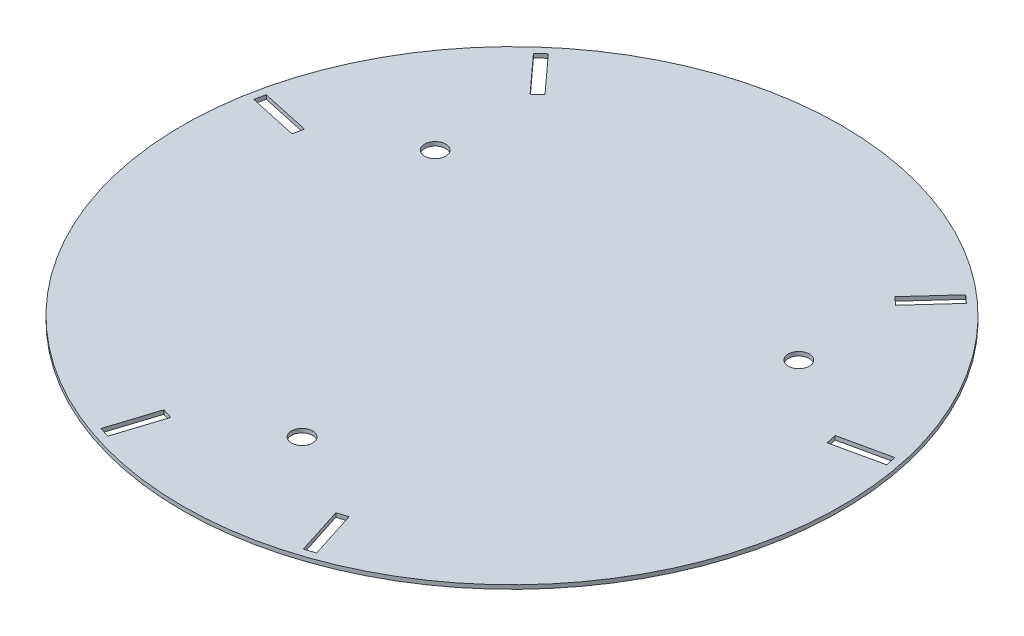
SolidWorks part; units mm, degrees
ref_plane "Front Plane" through (0, 0, 0) normal (0, 0, 1) x (1, 0, 0)
ref_plane "Top Plane" through (0, 0, 0) normal (0, 1, 0) x (1, 0, 0)
ref_plane "Right Plane" through (0, 0, 0) normal (1, 0, 0) x (0, 0, -1)
sketch "Sketch2" plane through (0, 0, 0) normal (0, 1, 0) x (1, 0, 0)
  circle A0 centre (0, 0) radius 125
  dimension "D1" = 250
extrude "Boss-Extrude1" add sketch "Sketch2" along normal blind 1.5 contours A0
sketch "Sketch3" plane through (0, 1.5, 0) normal (0, 1, 0) x (1, 0, 0)
  line L0 (0, 0) -> (-38, -119.084) construction
  line L1 (-270.1917, -358.6733) -> (-267.1917, -358.6733)
  line L2 (-270.1917, -358.6733) -> (-270.1917, -377.6733)
  line L3 (-270.1917, -377.6733) -> (-267.1917, -377.6733)
  line L4 (-267.1917, -358.6733) -> (-267.1917, -377.6733)
  line L9 (-38, -119.084) -> (38, -119.084) construction
  line L10 (0, 0) -> (0, -293.8403) construction
  line L11 (31.312, -98.1252) -> (35.1227, -96.9092)
  line L12 (37.088, -116.226) -> (40.8987, -115.01)
  line L14 (37.088, -116.226) -> (31.312, -98.1252)
  line L15 (40.8987, -115.01) -> (35.1227, -96.9092)
  line L17 (-38, -119.084) -> (-37.088, -116.226) construction
  line L19 (-37.088, -116.226) -> (-31.312, -98.1252)
  line L20 (-37.088, -116.226) -> (-40.8987, -115.01)
  line L21 (-31.312, -98.1252) -> (-35.1227, -96.9092)
  line L22 (-40.8987, -115.01) -> (-35.1227, -96.9092)
  line L52 (-82.1107, 90.2321) -> (-69.3229, 76.1796)
  line L53 (-82.1107, 90.2321) -> (-79.1522, 92.9243)
  line L54 (-79.1522, 92.9243) -> (-66.3645, 78.8717)
  line L55 (-69.3229, 76.1796) -> (-66.3645, 78.8717)
  line L56 (-100.6349, 21.9456) -> (-101.4872, 18.0375)
  line L57 (-120.0509, 22.0857) -> (-101.4872, 18.0375)
  line L58 (-119.1987, 25.9938) -> (-120.0509, 22.0857)
  line L59 (-119.1987, 25.9938) -> (-100.6349, 21.9456)
  line L60 (119.1987, 25.9938) -> (100.6349, 21.9456)
  line L61 (119.1987, 25.9938) -> (120.0509, 22.0857)
  line L62 (120.0509, 22.0857) -> (101.4872, 18.0375)
  line L63 (100.6349, 21.9456) -> (101.4872, 18.0375)
  line L64 (69.3229, 76.1796) -> (66.3645, 78.8717)
  line L65 (79.1522, 92.9243) -> (66.3645, 78.8717)
  line L66 (82.1107, 90.2321) -> (79.1522, 92.9243)
  line L67 (82.1107, 90.2321) -> (69.3229, 76.1796)
  circle A1 centre (0, 0) radius 125 construction
  point P18 (0, 0)
  point P38 (-15.7426, 25.0605)
  point P39 (0, 0)
  point P46 (-7.6333, 12.5317)
  dimension "D1" = 3
  dimension "D2" = 19
  dimension "D3" = 76
  dimension "D4" = 3
  dimension "D5" = 3
  dimension "D7" = 4
  dimension "D8" = 19
extrude "Cut-Extrude1" cut sketch "Sketch3" against normal through all
sketch "Sketch4" plane through (0, 1.5, 0) normal (0, 1, 0) x (1, 0, 0)
  circle A0 centre (0, -79.6391) radius 4
  circle A1 centre (-68.9695, 39.8196) radius 4
  circle A2 centre (68.9695, 39.8196) radius 4
  point P8 (0, 0)
  dimension "D1" = 3
extrude "Cut-Extrude2" cut sketch "Sketch4" against normal through all
